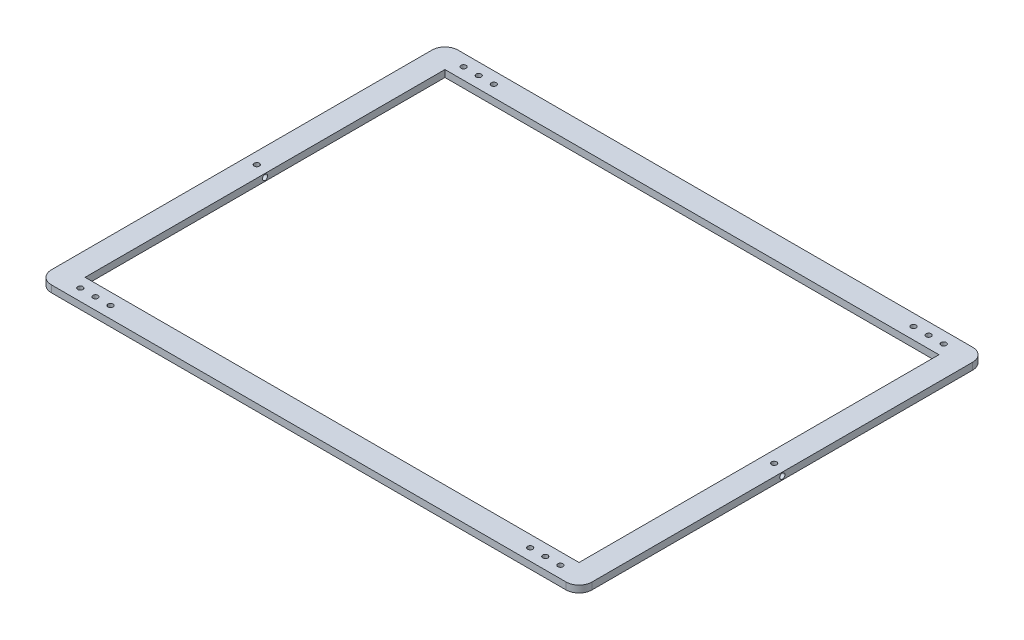
SolidWorks part; units mm, degrees
ref_plane "Спереди" through (0, 0, 0) normal (0, 0, 1) x (1, 0, 0)
ref_plane "Сверху" through (0, 0, 0) normal (0, 1, 0) x (1, 0, 0)
ref_plane "Справа" through (0, 0, 0) normal (1, 0, 0) x (0, 0, -1)
sketch "Эскиз1" plane through (0, 0, 0) normal (0, 1, 0) x (1, 0, 0)
  line L0 (0, 235) -> (0, -235) construction
  line L1 (-312.5, 235) -> (312.5, 235)
  line L2 (-312.5, 235) -> (-312.5, -235)
  line L3 (-312.5, -235) -> (312.5, -235)
  line L4 (312.5, 235) -> (312.5, -235)
  line L5 (-312.5, 0) -> (312.5, 0) construction
  line L6 (-285.5, 208) -> (285.5, 208)
  line L7 (285.5, 208) -> (285.5, -208)
  line L8 (-285.5, -208) -> (285.5, -208)
  line L9 (-285.5, 208) -> (-285.5, -208)
  dimension "D1" = 625
  dimension "D2" = 470
  dimension "D3" = 27
extrude "Бобышка-Вытянуть1" add sketch "Эскиз1" along normal mid plane 8
fillet "Скругление1" radius 15 4 edges at (312.5, 0, 235) (-312.5, 0, 235) (312.5, 0, -235) (-312.5, 0, -235)
ref_plane "Плоскость1" through (0, 0, -221.5) normal (0, 0, -1) x (-1, 0, 0)
ref_plane "Плоскость2" through (0, 0, 221.5) normal (0, 0, -1) x (-1, 0, 0)
ref_plane "Плоскость3" through (-299, 0, 0) normal (-1, 0, 0) x (0, 0, 1)
ref_plane "Плоскость4" through (299, 0, 0) normal (-1, 0, 0) x (0, 0, 1)
sketch "Эскиз2" plane through (0, 4, 0) normal (0, 1, 0) x (1, 0, 0)
  circle A0 centre (-277.5, -221.5) radius 3 construction
  circle A1 centre (-260, -221.5) radius 3 construction
  circle A2 centre (-242.5, -221.5) radius 3 construction
  circle A3 centre (242.5, -221.5) radius 3 construction
  circle A4 centre (260, -221.5) radius 3 construction
  circle A5 centre (277.5, -221.5) radius 3 construction
  circle A6 centre (242.5, 221.5) radius 3 construction
  circle A7 centre (260, 221.5) radius 3 construction
  circle A8 centre (277.5, 221.5) radius 3 construction
  circle A9 centre (-277.5, 221.5) radius 3 construction
  circle A10 centre (-260, 221.5) radius 3 construction
  circle A11 centre (-242.5, 221.5) radius 3 construction
  circle A12 centre (-277.5, -221.5) radius 3
  circle A13 centre (-260, -221.5) radius 3
  circle A14 centre (-242.5, -221.5) radius 3
  circle A15 centre (242.5, -221.5) radius 3
  circle A16 centre (260, -221.5) radius 3
  circle A17 centre (277.5, -221.5) radius 3
  circle A18 centre (242.5, 221.5) radius 3
  circle A19 centre (260, 221.5) radius 3
  circle A20 centre (277.5, 221.5) radius 3
  circle A21 centre (-277.5, 221.5) radius 3
  circle A22 centre (-260, 221.5) radius 3
  circle A23 centre (-242.5, 221.5) radius 3
extrude "Вырез-Вытянуть1" cut sketch "Эскиз2" against normal through all
sketch "Эскиз3" plane through (0, 0, 0) normal (1, 0, 0) x (0, 0, -1)
  circle A0 centre (0, 0) radius 3
  dimension "D1" = 6
extrude "Вырез-Вытянуть2" cut sketch "Эскиз3" against normal through all and the other way through all
sketch "Эскиз4" plane through (0, 4, 0) normal (0, 1, 0) x (1, 0, 0)
  line L0 (-299, 4.4) -> (-299, -4.4) construction
  line L1 (299, 4.4) -> (299, -4.4) construction
  circle A0 centre (-299, 4) radius 3
  circle A1 centre (299, 4) radius 3
  dimension "D1" = 6
  dimension "D2" = 4
extrude "Вырез-Вытянуть3" cut sketch "Эскиз4" against normal through all
